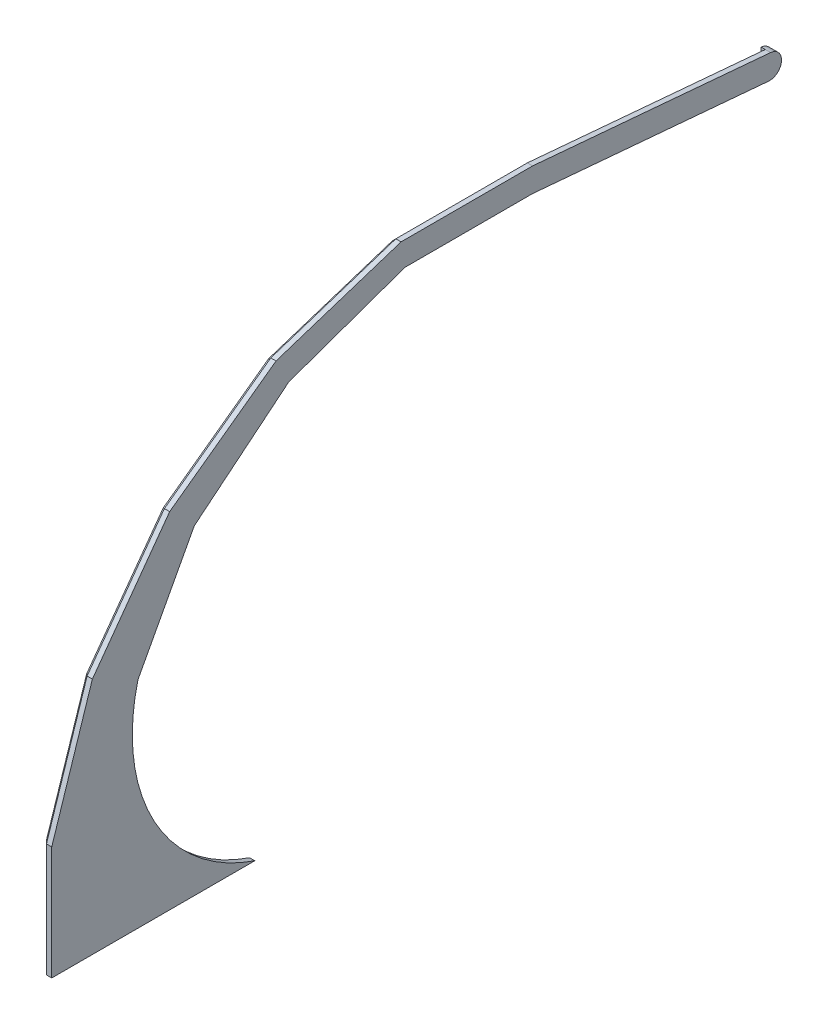
SolidWorks part; units mm, degrees
ref_plane "Front Plane" through (0, 0, 0) normal (0, 0, 1) x (1, 0, 0)
ref_plane "Top Plane" through (0, 0, 0) normal (0, 1, 0) x (1, 0, 0)
ref_plane "Right Plane" through (0, 0, 0) normal (1, 0, 0) x (0, 0, -1)
sketch "Sketch1" plane through (0, 0, 0) normal (1, 0, 0) x (0, 0, -1)
  line L0 (12.6153, -92.6333) -> (182.6153, -92.6333)
  line L6 (415.1195, 274.7215) -> (612.6153, 257.4428)
  line L8 (614.3584, 277.3667) -> (415.1195, 294.7979)
  line L9 (12.6153, -92.6333) -> (12.6153, 2.3615)
  line L10 (12.6153, 2.3615) -> (46.6281, 107.0421)
  line L11 (46.6281, 107.0421) -> (111.3243, 196.0888)
  line L12 (111.3243, 196.0888) -> (200.371, 260.7851)
  line L13 (200.371, 260.7851) -> (305.0517, 294.7979)
  line L14 (305.0517, 294.7979) -> (415.1195, 294.7979)
  line L15 (452.6153, 271.441) -> (183.2145, -92.6333) construction
  line L16 (452.6153, 271.441) -> (634.136, -92.6333) construction
  line L20 (84.8259, 87.5794) -> (131.9298, 175.4834)
  line L21 (131.9298, 175.4834) -> (210.8849, 240.1505)
  line L22 (210.8849, 240.1505) -> (308.2365, 274.69)
  line L23 (308.2365, 274.69) -> (415.1195, 274.7215)
  line L24 (111.3243, 196.0888) -> (131.9298, 175.4834) construction
  line L25 (200.371, 260.7851) -> (210.8849, 240.1505) construction
  line L26 (46.6281, 107.0421) -> (84.8259, 87.5794) construction
  line L27 (183.2145, -92.6333) -> (634.136, -92.6333) construction
  line L28 (305.0517, 294.7979) -> (308.2365, 274.69) construction
  arc A0 (84.8259, 87.5794) -> (182.6153, -92.6333) centre (230.5143, 49.9965) ccw
  arc A2 (612.6153, 257.4428) -> (614.3584, 277.3667) centre (613.4869, 267.4048) ccw
  dimension "D1" = 600
  dimension "D2" = 200
  dimension "D3" = 5
  dimension "D4" = 370
  dimension "D5" = 20
  dimension "D12" = 162
  dimension "D13" = 162
  dimension "D14" = 162
  dimension "D15" = 162
  dimension "D16" = 170
  dimension "D18" = 63
  dimension "D19" = 58.5
  dimension "D20" = 160
  dimension "D6" = 81
  dimension "D7" = 81
  dimension "D8" = 81
  dimension "D17" = 162
  dimension "D21" = 81
extrude "Boss-Extrude1" add sketch "Sketch1" against normal blind 4.4
sketch "Sketch2" plane through (-4.4, 0, 0) normal (-1, 0, 0) x (0, 0, 1)
  line L0 (-614.3584, 277.3667) -> (-614.0534, 273.88)
  line L1 (-614.0534, 273.88) -> (-415.1195, 291.2845)
  line L2 (-612.9203, 260.9295) -> (-415.2718, 278.2215)
  line L3 (-612.9203, 260.9295) -> (-612.6153, 257.4428)
  line L4 (-415.1195, 294.7979) -> (-415.1195, 274.7215) construction
  line L5 (-305.0517, 294.7979) -> (-308.2365, 274.69) construction
  line L6 (-200.371, 260.7851) -> (-210.8849, 240.1505) construction
  line L7 (-415.1195, 291.2845) -> (-305.6082, 291.2845)
  line L8 (-415.2718, 278.2215) -> (-307.6822, 278.1898)
  line L9 (-307.6822, 278.1898) -> (-209.2898, 243.2811)
  line L10 (-305.6082, 291.2845) -> (-201.9859, 257.6156)
  line L11 (-111.3243, 196.0888) -> (-131.9298, 175.4834) construction
  line L12 (-46.6281, 107.0421) -> (-84.8259, 87.5794) construction
  line L13 (-12.6153, 2.3615) -> (4.2768, 3.0013) construction
  line L14 (-201.9859, 257.6156) -> (-113.8396, 193.5735)
  line L15 (-113.8396, 193.5735) -> (-49.7976, 105.4272)
  line L16 (-49.7976, 105.4272) -> (-16.2646, 2.2232)
  line L17 (-16.2646, 2.2232) -> (-16.2646, -92.6333)
  line L18 (-12.6153, -92.6333) -> (-182.6153, -92.6333) construction
  line L19 (-16.2646, -92.6333) -> (-101.9058, -92.6333)
  line L20 (-101.9058, -92.6333) -> (-66.5859, 0.3173)
  line L21 (-66.5859, 0.3173) -> (-81.7074, 89.1683)
  line L22 (-81.7074, 89.1683) -> (-129.4906, 177.9226)
  line L23 (-129.4906, 177.9226) -> (-209.2898, 243.2811)
  line L26 (-415.1195, 294.7979) -> (-305.0517, 294.7979) construction
  line L27 (-308.2365, 274.69) -> (-415.1195, 274.7215) construction
  line L28 (-614.3584, 277.3667) -> (-415.1195, 294.7979) construction
  line L29 (-415.1195, 274.7215) -> (-612.6153, 257.4428) construction
  line L30 (-305.0517, 294.7979) -> (-200.371, 260.7851) construction
  line L31 (-210.8849, 240.1505) -> (-308.2365, 274.69) construction
  line L32 (-200.371, 260.7851) -> (-111.3243, 196.0888) construction
  line L33 (-131.9298, 175.4834) -> (-210.8849, 240.1505) construction
  line L34 (-111.3243, 196.0888) -> (-46.6281, 107.0421) construction
  line L36 (-46.6281, 107.0421) -> (-12.6153, 2.3615) construction
  line L37 (-12.6153, 2.3615) -> (-12.6153, -92.6333) construction
  line L39 (-573.6826, 271.3891) -> (-563.123, 272.3129)
  line L40 (-573.6826, 271.3891) -> (-573.3253, 267.3047)
  line L41 (-573.3253, 267.3047) -> (-562.7656, 268.2286)
  line L42 (-563.123, 272.3129) -> (-562.7656, 268.2286)
  line L43 (-523.2752, 275.7992) -> (-512.7155, 276.723)
  line L44 (-523.2752, 275.7992) -> (-522.9179, 271.7148)
  line L45 (-522.9179, 271.7148) -> (-512.3582, 272.6386)
  line L46 (-512.7155, 276.723) -> (-512.3582, 272.6386)
  line L47 (-618.9454, 268.985) -> (-608.3857, 269.9089)
  line L48 (-618.9454, 268.985) -> (-618.588, 264.9006)
  line L49 (-618.588, 264.9006) -> (-608.0283, 265.8245)
  line L50 (-608.3857, 269.9089) -> (-608.0283, 265.8245)
  arc A0 (-614.3584, 277.3667) -> (-612.6153, 257.4428) centre (-613.4869, 267.4048) ccw
  point P79 (-307.7277, 277.9337)
  point P80 (-409.5629, 278.3898)
  dimension "D1" = 3.5
  dimension "D2" = 3.5
  dimension "D3" = 4.1
  dimension "D4" = 10.6
  dimension "D5" = 40
  dimension "D6" = 4.1
  dimension "D7" = 10.6
  dimension "D8" = 40
  dimension "D9" = 9.5
  dimension "D10" = 9.5
  dimension "D11" = 10.6
  dimension "D12" = 5.3
  dimension "D13" = 4.1
  dimension "D14" = 2.05
  dimension "D15" = 3.5
  dimension "D16" = 3.5
extrude "Boss-Extrude2" add sketch "Sketch2" along normal blind 3.5
equation "\"Phone height\"= 370"
equation "\"edge distance from wall\"= 600"
equation "\"phone angle\"= 5"
equation "\"D1@Sketch1\"=\"edge distance from wall\""
equation "\"base depth\"= 170"
equation "\"width\"= 108"
equation "\"Phone segment length\"= 200"
equation "\"D2@Sketch1\"=\"Phone segment length\""
equation "\"D3@Sketch1\"=\"phone angle\""
equation "\"D4@Sketch1\"=\"Phone height\""
equation "\"Phone segment thick\"= 20"
equation "\"D5@Sketch1\"=\"Phone segment thick\""
equation "\"Phone segment acute angle\"= 1"
equation "\"D16@Sketch1\"=\"base depth\""
equation "\"upper segment count\"= 6"
equation "\"lower segment count\"= 5"
equation "\"upper segment angle\"= 180 - ( 90 / ( \"upper segment count\" - 1 ) )"
equation "\"D12@Sketch1\"=\"upper segment angle\""
equation "\"D13@Sketch1\"=\"upper segment angle\""
equation "\"D14@Sketch1\"=\"upper segment angle\""
equation "\"D15@Sketch1\"=\"upper segment angle\""
equation "\"lower segment angle\"= 180 - ( 90 / ( \"lower segment count\" - 1 ) )"
equation "\"fov\"=63"
equation "\"D18@Sketch1\"=\"fov\""
equation "\"D19@Sketch1\"=(180-\"fov\")/2"
equation "\"D6@Sketch1\"=\"upper segment angle\"/2"
equation "\"D7@Sketch1\"=\"upper segment angle\"/2"
equation "\"D8@Sketch1\"=\"upper segment angle\"/2"
equation "\"D17@Sketch1\"=\"upper segment angle\""
equation "\"D21@Sketch1\"=\"upper segment angle\"/2"
equation "\"Thicker acrylic\"= 4.4"
equation "\"Thinner acrylic\"= 3.5"
equation "\"D1@Boss-Extrude1\"=\"Thicker acrylic\""
equation "\"D1@Sketch2\"=\"Thinner acrylic\""
equation "\"D2@Sketch2\"=\"Thinner acrylic\""
equation "\"phone thick\"= 9.5"
equation "\"phone support width\"= 10"
equation "\"fit\" = 0.6"
equation "\"D3@Sketch2\"=\"Thinner acrylic\"+\"fit\""
equation "\"D4@Sketch2\"=\"phone support width\"+\"fit\""
equation "\"D5@Sketch2\"=40"
equation "\"D6@Sketch2\"=\"Thinner acrylic\"+\"fit\""
equation "\"D7@Sketch2\"=\"phone support width\"+\"fit\""
equation "\"D9@Sketch2\"=\"phone thick\""
equation "\"D10@Sketch2\"=\"phone thick\""
equation "\"D1@Boss-Extrude2\"=\"Thinner acrylic\""
equation "\"D11@Sketch2\"=\"phone support width\"+\"fit\""
equation "\"D12@Sketch2\"=\"D11@Sketch2\"/2"
equation "\"D13@Sketch2\"=\"Thinner acrylic\"+\"fit\""
equation "\"D14@Sketch2\"=\"D13@Sketch2\"/2"
equation "\"phone support length\"= 98.5"
equation "\"D15@Sketch2\"=\"Thinner acrylic\""
equation "\"D16@Sketch2\"=\"Thinner acrylic\""
